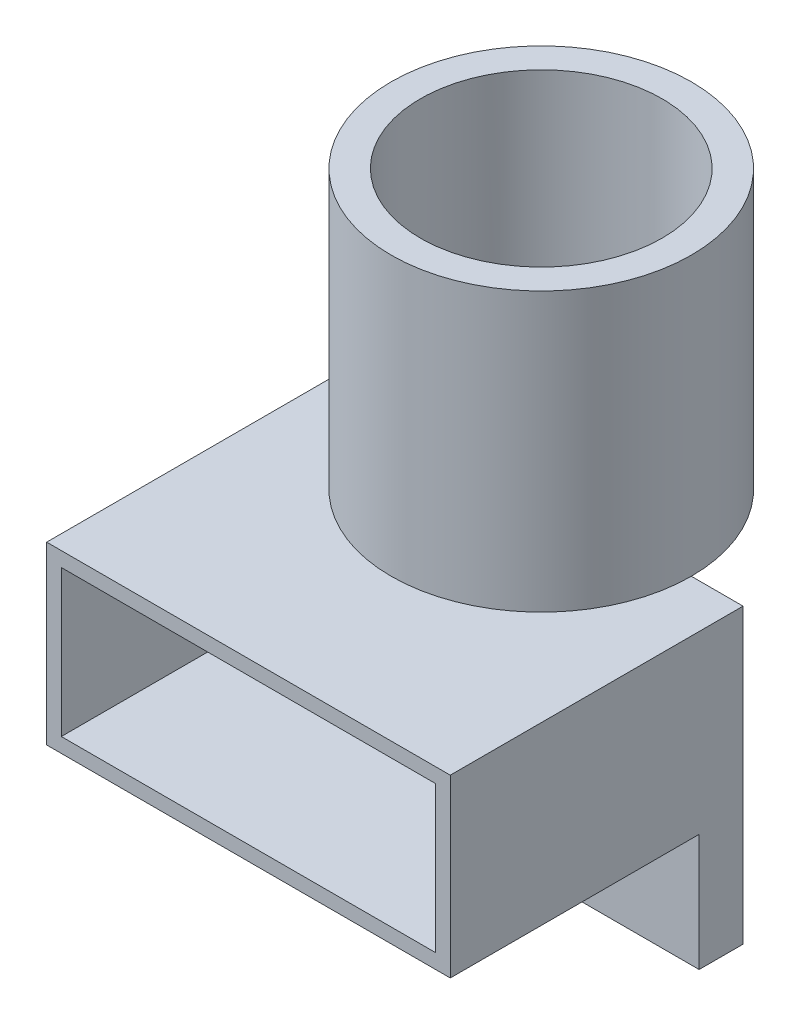
SolidWorks part; units mm, degrees
ref_plane "前基準面" through (0, 0, 0) normal (0, 0, 1) x (1, 0, 0)
ref_plane "上基準面" through (0, 0, 0) normal (0, 1, 0) x (1, 0, 0)
ref_plane "右基準面" through (0, 0, 0) normal (1, 0, 0) x (0, 0, -1)
sketch "刪除圖檔" plane through (0, 0, 0) normal (0, 1, 0) x (1, 0, 0)
  circle A0 centre (0, 0) radius 13.785 construction
  dimension "D1" = 27.57
sketch "草圖2" plane through (0, 0, 0) normal (0, 1, 0) x (1, 0, 0)
  circle A0 centre (0, 0) radius 10.255
  dimension "D1" = 20.51
extrude "19mm" add sketch "草圖2" along normal blind 19 thin thin type one direction reverse wall 2
sketch "草圖13" plane through (0, 0, 0) normal (0, 1, 0) x (1, 0, 0)
  line L0 (-1000, 0) -> (49000, 0) construction
  arc A0 (-8.255, 0) -> (8.255, 0) centre (0, 0) ccw
extrude "伸長-薄件3" add sketch "草圖13" against normal blind 11 thin thin type one direction wall 2
sketch "聲音元件" plane through (0, 0, 0) normal (0, 0, 1) x (1, 0, 0)
  line L0 (13.785, 0) -> (-13.785, 0) construction
  line L1 (-13.785, 0) -> (13.785, 0)
  line L2 (-13.785, 0) -> (-13.785, -12)
  line L3 (-13.785, -12) -> (13.785, -12)
  line L4 (13.785, 0) -> (13.785, -12)
  dimension "D1" = 12
extrude "盒子 伸長 " add sketch "聲音元件" along normal blind 20
sketch "草圖6" plane through (0, 0, 20) normal (0, 0, 1) x (1, 0, 0)
  line L0 (-13.785, 0) -> (-13.785, -12) construction
  line L1 (-12.785, -1) -> (12.785, -1)
  line L2 (-12.785, -1) -> (-12.785, -11)
  line L3 (-12.785, -11) -> (12.785, -11)
  line L4 (12.785, -1) -> (12.785, -11)
  line L5 (13.785, -12) -> (13.785, 0) construction
  line L6 (13.785, 0) -> (-13.785, 0) construction
  line L7 (-13.785, -12) -> (13.785, -12) construction
  dimension "D1" = 1
  dimension "D2" = 1
  dimension "D3" = 1
  dimension "D4" = 1
extrude "除料-伸長1" cut sketch "草圖6" against normal blind 15
fillet "圓角1" radius 5 1 edges at (0, 0, 0)
sketch "草圖10" plane through (0, -12, 0) normal (0, -1, 0) x (1, 0, 0)
  line L1 (-13.785, 0) -> (13.785, 0)
  line L2 (-13.785, 0) -> (-13.785, 3)
  line L3 (-13.785, 3) -> (13.785, 3)
  line L4 (13.785, 0) -> (13.785, 3)
  dimension "D1" = 3
extrude "填料-伸長3" add sketch "草圖10" along normal blind 8
